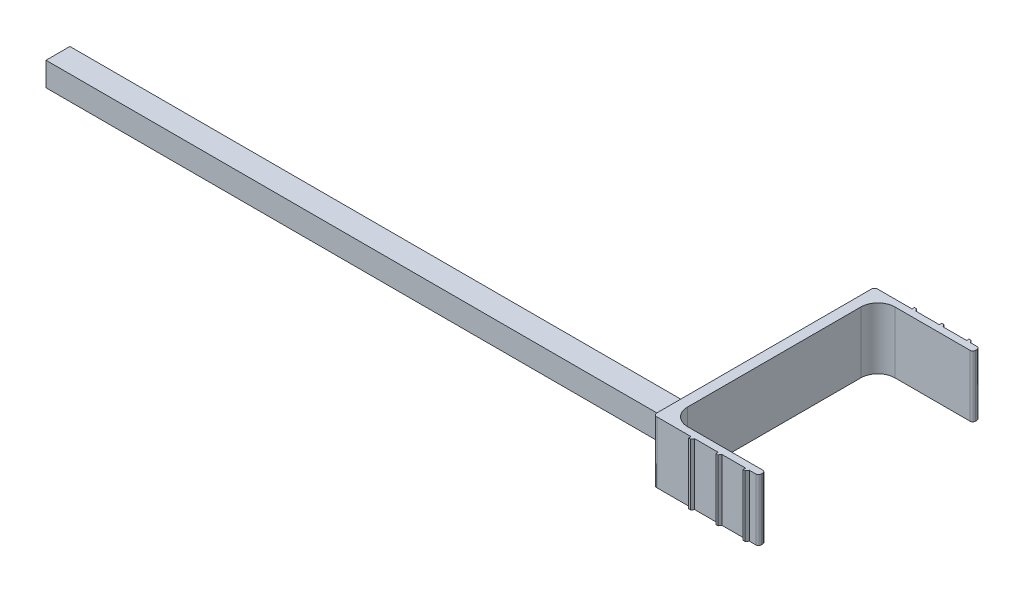
SolidWorks part; units mm, degrees
ref_plane "Front Plane" through (0, 0, 0) normal (0, 0, 1) x (1, 0, 0)
ref_plane "Top Plane" through (0, 0, 0) normal (0, 1, 0) x (1, 0, 0)
ref_plane "Right Plane" through (0, 0, 0) normal (1, 0, 0) x (0, 0, -1)
sketch "Sketch1" plane through (0, 0, 0) normal (0, 1, 0) x (1, 0, 0)
  line L2 (7.0534, -32.3877) -> (18.0534, -32.3877)
  line L6 (10.0534, -30.3877) -> (37.0534, -30.3877)
  line L7 (37.8534, -31.1877) -> (37.8534, -31.5877)
  line L8 (10.0534, -30.3877) -> (10.0534, 0)
  line L11 (26.0534, -33.0877) -> (26.0534, -32.3877)
  line L12 (18.6514, -33.0877) -> (18.0534, -33.0877)
  line L13 (18.6514, -33.0877) -> (19.1514, -32.3877)
  line L14 (18.0534, -33.0877) -> (18.0534, -32.3877)
  line L15 (26.6514, -33.0877) -> (26.0534, -33.0877)
  line L16 (26.6514, -33.0877) -> (27.1514, -32.3877)
  line L17 (34.0534, -33.0877) -> (34.0534, -32.3877)
  line L18 (34.6514, -33.0877) -> (34.0534, -33.0877)
  line L19 (34.6514, -33.0877) -> (35.1514, -32.3877)
  line L65 (19.1514, -32.3877) -> (26.0534, -32.3877)
  line L66 (27.1514, -32.3877) -> (34.0534, -32.3877)
  line L67 (35.1514, -32.3877) -> (37.0534, -32.3877)
  line L179 (7.0534, 0) -> (10.0534, 0)
  line L180 (7.0534, 0) -> (7.0534, -32.3877)
  line L181 (7.0534, -20.3877) -> (-182.9466, -20.3877)
  line L182 (7.0534, -13.3877) -> (-182.9466, -13.3877)
  line L183 (-182.9466, -20.3877) -> (-182.9466, -13.3877)
  line L184 (7.0534, -20.3877) -> (7.0534, -13.3877)
  arc A2 (37.0534, -32.3877) -> (37.8534, -31.5877) centre (37.0534, -31.5877) ccw
  arc A3 (37.0534, -30.3877) -> (37.8534, -31.1877) centre (37.0534, -31.1877) cw
  dimension "D3" = 0.8
  dimension "D7" = 11
  dimension "D11" = 190
  dimension "D20" = 8
  dimension "D4" = 2
  dimension "D5" = 3
  dimension "D6" = 32.3877
  dimension "D8" = 7
  dimension "D9" = 30
  dimension "D10" = 12
  dimension "D14" = 0.7
  dimension "D15" = 1.098
  dimension "D17" = 0.5
  dimension "D18" = 0.598
  dimension "D19" = 3
extrude "Boss-Extrude1" add sketch "Sketch1" along normal blind 18 contours A3 L6 L8 L179 L180 L2 L14 L12 L13 L65 L11 L15 L16 L66 L17 L18 L19 L67 A2 L7 region at (7.5054, 0, 26.3877)
fillet "Fillet1" radius 5 1 edges at (10.0534, 9, 30.3877)
fillet "Fillet2" radius 1 1 edges at (7.0534, 9, 32.3877)
mirror "Mirror1" about plane through (0, 18, 0) normal (0, 0, -1) of bodies 101
extrude "Boss-Extrude2" add sketch "Sketch1<3>" along normal blind 7 contours L183 L181 L180 L182 region at (-87.9466, 0, 16.8877)
sketch "Sketch1<3>" plane through (0, 0, 0) normal (0, 1, 0) x (1, 0, 0) same geometry as "Sketch1"
fillet "Fillet3" radius 10 3 edges at (7.0534, 3.5, 20.3877) (7.0534, 3.5, 13.3877) (7.0534, 7, 16.8877)
